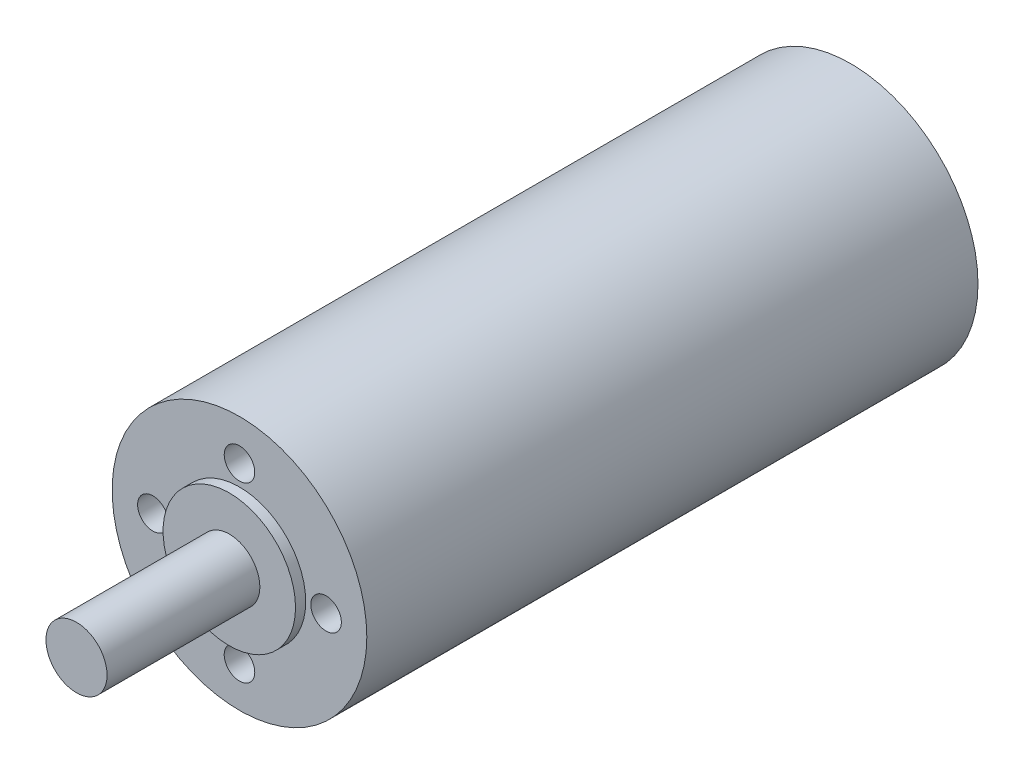
SolidWorks part; units mm, degrees
ref_plane "Plano frontal" through (0, 0, 0) normal (0, 0, 1) x (1, 0, 0)
ref_plane "Plano superior" through (0, 0, 0) normal (0, 1, 0) x (1, 0, 0)
ref_plane "Plano direito" through (0, 0, 0) normal (1, 0, 0) x (0, 0, -1)
sketch "Esboço1" plane through (0, 0, 0) normal (0, 0, 1) x (1, 0, 0)
  circle A0 centre (0, 0) radius 12.5
  dimension "D1" = 25
extrude "Ressalto-extrusão1" add sketch "Esboço1" along normal blind 60
sketch "Esboço2" plane through (0, 0, 60) normal (0, 0, 1) x (1, 0, 0)
  circle A0 centre (0, 0) radius 6.5
  dimension "D1" = 13
extrude "Ressalto-extrusão2" add sketch "Esboço2" along normal blind 1
sketch "Esboço3" plane through (0, 0, 61) normal (0, 0, 1) x (1, 0, 0)
  circle A0 centre (0, 0) radius 3
  dimension "D1" = 6
extrude "Ressalto-extrusão3" add sketch "Esboço3" along normal blind 15
sketch "Esboço4" plane through (0, 0, 60) normal (0, 0, 1) x (1, 0, 0)
  line L0 (0, -8.5) -> (0, 0) construction
  circle A0 centre (0, -8.5) radius 1.5
  dimension "D1" = 3
  dimension "D2" = 8.5
extrude "Corte-extrusão1" cut sketch "Esboço4" against normal blind 4
pattern_circular "PadrãoCircular1" count 4 over 360 about axis through (0, 0, 76) along (0, 0, -1) of "Corte-extrusão1"
